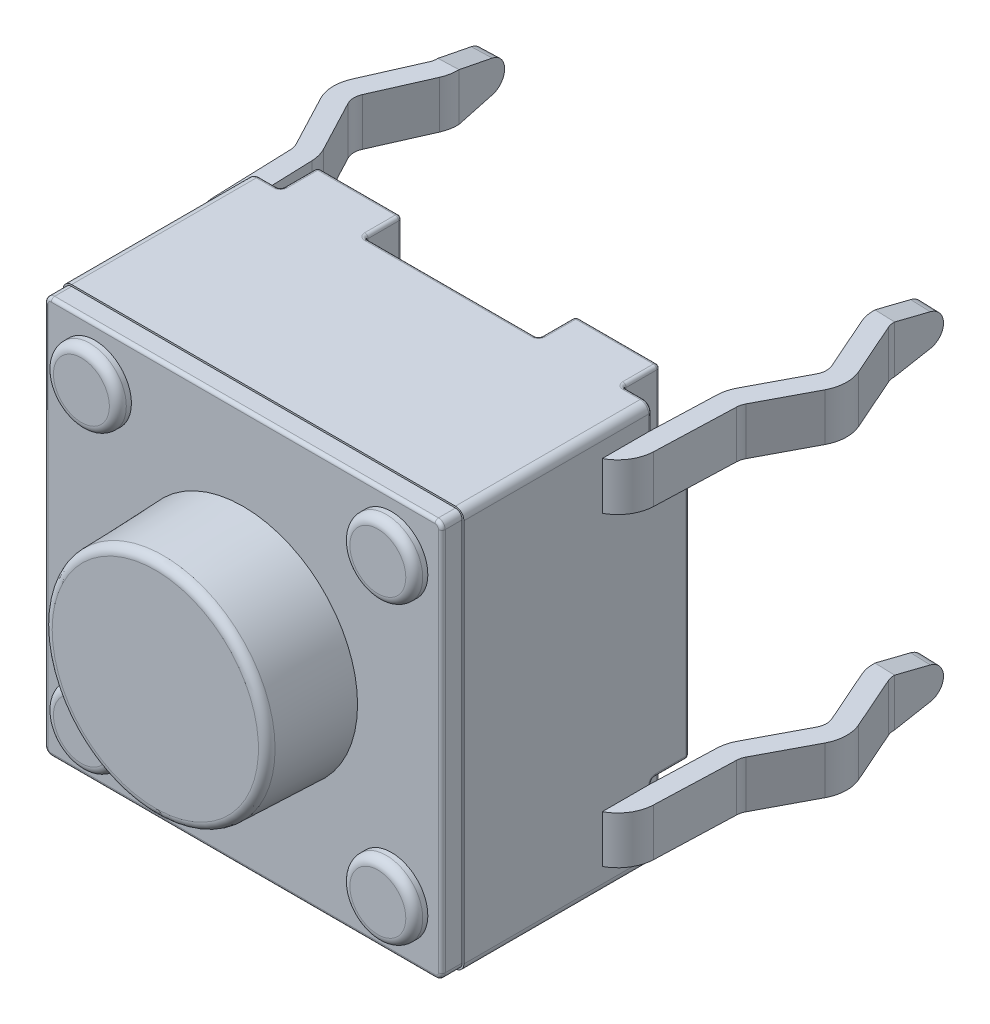
SolidWorks part; units mm, degrees
ref_plane "Front Plane" through (0, 0, 0) normal (0, 0, 1) x (1, 0, 0)
ref_plane "Top Plane" through (0, 0, 0) normal (0, 1, 0) x (1, 0, 0)
ref_plane "Right Plane" through (0, 0, 0) normal (1, 0, 0) x (0, 0, -1)
sketch "Sketch1" plane through (0, 0, 0) normal (0, 0, 1) x (1, 0, 0)
  line L1 (-3.0035, -3.0035) -> (3.0035, -3.0035)
  line L2 (-3.0035, -3.0035) -> (-3.0035, 3.0036)
  line L3 (-3.0035, 3.0036) -> (3.0035, 3.0036)
  line L4 (3.0035, -3.0035) -> (3.0035, 3.0036)
  line L5 (-3.0035, -3.0035) -> (3.0035, 3.0036) construction
  line L6 (-3.0035, 3.0036) -> (3.0035, -3.0035) construction
  point P0 (0, 0)
  dimension "D1" = 6.0071
  dimension "D2" = 6.0071
extrude "Boss-Extrude1" add sketch "Sketch1" along normal blind 2.8194 from offset 0.5588
fillet "Fillet1" radius 0.127 4 edges at (-3.0035, -3.0035, 1.9685) (-3.0035, 3.0036, 1.9685) (3.0035, 3.0036, 1.9685) (3.0035, -3.0035, 1.9685)
sketch "Sketch2" plane through (0, 0, 3.3782) normal (0, 0, -1) x (-1, 0, 0)
  line L8 (2.9781, -2.8765) -> (2.9781, 2.8765)
  line L9 (-2.8765, -2.9781) -> (2.8765, -2.9781)
  line L10 (-2.9781, 2.8765) -> (-2.9781, -2.8765)
  line L11 (2.8765, 2.9782) -> (-2.8765, 2.9782)
  line L12 (2.9781, -2.8765) -> (2.9781, 2.8765)
  line L13 (-2.8765, -2.9781) -> (2.8765, -2.9781)
  line L14 (-2.9781, 2.8765) -> (-2.9781, -2.8765)
  line L15 (2.8765, 2.9782) -> (-2.8765, 2.9782)
  arc A8 (2.8765, -2.9781) -> (2.9781, -2.8765) centre (2.8765, -2.8765) ccw
  arc A9 (-2.9781, -2.8765) -> (-2.8765, -2.9781) centre (-2.8765, -2.8765) ccw
  arc A10 (-2.8765, 2.9782) -> (-2.9781, 2.8765) centre (-2.8765, 2.8766) ccw
  arc A11 (2.9781, 2.8765) -> (2.8765, 2.9782) centre (2.8765, 2.8765) ccw
  arc A12 (2.8765, -2.9781) -> (2.9781, -2.8765) centre (2.8765, -2.8765) ccw
  arc A13 (-2.9781, -2.8765) -> (-2.8765, -2.9781) centre (-2.8765, -2.8765) ccw
  arc A14 (-2.8765, 2.9782) -> (-2.9781, 2.8765) centre (-2.8765, 2.8766) ccw
  arc A15 (2.9781, 2.8765) -> (2.8765, 2.9782) centre (2.8765, 2.8765) ccw
  dimension "D1" = 0.0254
extrude "Boss-Extrude2" add sketch "Sketch2" against normal blind 0.3048
sketch "Sketch3" plane through (0, 0, 0) normal (0, 0, 1) x (1, 0, 0)
  line L0 (-2.5662, -3.0035) -> (-2.5662, -1.8948)
  line L1 (-2.8765, -3.0035) -> (2.8765, -3.0035) construction
  line L2 (-2.5662, -1.8948) -> (-3.0035, -1.8948)
  line L3 (-3.0035, 2.8765) -> (-3.0035, -2.8765) construction
  line L4 (-2.4413, -0.5609) -> (-1.3018, -0.5609)
  line L5 (-1.3018, -0.5609) -> (-1.3017, -3.0035)
  line L6 (-2.4413, -0.5609) -> (-2.4413, 0.5609)
  line L7 (-2.5662, -3.0035) -> (-1.3017, -3.0035)
  line L8 (-3.0035, -1.8948) -> (-3.0035, 1.8948)
  line L9 (-2.4413, 0) -> (-3.0035, 0) construction
  line L10 (-2.5662, 3.0036) -> (-1.3017, 3.0035)
  line L11 (-1.3017, 0.5609) -> (-1.3017, 3.0035)
  line L12 (-2.4413, 0.5609) -> (-1.3017, 0.5609)
  line L13 (-2.5662, 1.8948) -> (-3.0035, 1.8948)
  line L14 (-2.5662, 3.0036) -> (-2.5662, 1.8948)
  line L15 (0, -3.0035) -> (0, 3.0036) construction
  line L16 (2.8765, 3.0036) -> (-2.8765, 3.0036) construction
  line L17 (2.4413, 0) -> (3.0035, 0) construction
  line L18 (2.5662, 3.0035) -> (2.5662, 1.8948)
  line L19 (2.5662, 1.8948) -> (3.0035, 1.8948)
  line L20 (2.4413, 0.5609) -> (1.3017, 0.5609)
  line L21 (1.3017, 0.5609) -> (1.3017, 3.0035)
  line L22 (2.5662, 3.0035) -> (1.3017, 3.0035)
  line L23 (3.0035, -1.8948) -> (3.0035, 1.8948)
  line L24 (2.5662, -3.0036) -> (1.3017, -3.0036)
  line L25 (2.4413, -0.5609) -> (2.4413, 0.5609)
  line L26 (1.3017, -0.5609) -> (1.3017, -3.0036)
  line L27 (2.4413, -0.5609) -> (1.3017, -0.5609)
  line L28 (2.5662, -1.8948) -> (3.0035, -1.8948)
  line L29 (2.5662, -3.0036) -> (2.5662, -1.8948)
  dimension "D1" = 1.7018
extrude "Boss-Extrude3" add sketch "Sketch3" along normal up to next
sketch "Sketch4" plane through (0, 0, 3.683) normal (0, 0, 1) x (1, 0, 0)
  line L1 (-2.2217, -2.2129) -> (2.2217, -2.2129) construction
  line L2 (-2.2217, -2.2129) -> (-2.2217, 2.2129) construction
  line L3 (-2.2217, 2.2129) -> (2.2217, 2.2129) construction
  line L4 (2.2217, -2.2129) -> (2.2217, 2.2129) construction
  line L5 (-2.2217, -2.2129) -> (2.2217, 2.2129) construction
  line L6 (-2.2217, 2.2129) -> (2.2217, -2.2129) construction
  circle A0 centre (2.2217, 2.2129) radius 0.5461
  circle A1 centre (-2.2217, 2.2129) radius 0.5461
  circle A2 centre (-2.2217, -2.2129) radius 0.5461
  circle A3 centre (2.2217, -2.2129) radius 0.5461
  point P0 (0, 0)
  dimension "D1" = 1.0922
extrude "Boss-Extrude4" add sketch "Sketch4" along normal blind 0.2032
sketch "Sketch5" plane through (0, 0, 3.683) normal (0, 0, 1) x (1, 0, 0)
  circle A0 centre (0, 0) radius 1.7145
  dimension "D1" = 3.429
extrude "Boss-Extrude5" add sketch "Sketch5" along normal offset from surface 5 draft 2
fillet "Fillet2" radius 0.127 5 edges at (-1.6756, 2.2129, 3.8862) (-1.6756, -2.2129, 3.8862) (2.7678, 2.2129, 3.8862) (2.7678, -2.2129, 3.8862) (-1.6685, 0, 5)
fillet "Fillet3" radius 0.0508 88 edges at (2.9664, -2.9664, 0.5588) (2.9664, 2.9664, 0.5588) (-2.9664, 2.9664, 0.5588) (-2.9664, -2.9664, 0.5588) (3.0035, -2.3857, 0.5588) (3.0035, 2.3857, 0.5588) (1.3017, -3.0036, 0.2794) (1.3017, 3.0035, 0.2794) (2.9484, 2.9484, 3.683) (0, 2.9782, 3.683) (-2.9484, 2.9484, 3.683) (-2.9781, 0, 3.683) (-2.9484, -2.9484, 3.683) (0, -2.9781, 3.683) (2.9484, -2.9484, 3.683) (2.4413, -0.5609, 0.2794) (1.3017, -0.5609, 0.2794) (1.3017, 0.5609, 0.2794) (2.4413, 0.5609, 0.2794) (-1.3018, -0.5609, 0.2794) (-2.4413, -0.5609, 0.2794) (-2.4413, 0.5609, 0.2794) (-1.3017, 0.5609, 0.2794) (2.7849, -1.8948, 0.5588) (3.0035, -1.8948, 0.2794) (2.5662, -3.0036, 0.2794) (2.5662, -2.4492, 0.5588) (2.5662, -1.8948, 0.2794) (3.0035, 1.8948, 0.2794) (2.7849, 1.8948, 0.5588) (2.5662, 1.8948, 0.2794) (2.5662, 2.4492, 0.5588) (2.5662, 3.0035, 0.2794) (-2.5662, 1.8948, 0.2794) (-2.5662, -1.8948, 0.2794) (-1.8715, 0.5609, 0.5588) (-2.4413, 0, 0.5588) (-1.8715, -0.5609, 0.5588) (1.3017, -1.7822, 0.5588) (1.8715, -0.5609, 0.5588) (2.4413, 0, 0.5588) (1.8715, 0.5609, 0.5588) (1.3017, 1.7822, 0.5588) (-1.3017, -1.7822, 0) (-1.8715, -0.5609, 0) (-2.4413, 0, 0) (-1.8715, 0.5609, 0) (-1.3017, 1.7822, 0) (-1.934, 3.0035, 0) (-2.5662, 2.4492, 0) (-2.7849, 1.8948, 0) (-3.0035, 0, 0) (-2.7849, -1.8948, 0) (-2.5662, -2.4492, 0) (-1.934, -3.0035, 0) (1.3017, 1.7822, 0) (1.8715, 0.5609, 0) (2.4413, 0, 0) (1.8715, -0.5609, 0) (1.3017, -1.7822, 0) (1.934, -3.0036, 0) (2.5662, -2.4492, 0) (2.7849, -1.8948, 0) (3.0035, 0, 0) (2.7849, 1.8948, 0) (2.5662, 2.4492, 0) (1.934, 3.0035, 0) (2.9781, 0, 3.683)
sketch "Sketch6" plane through (0, -3.0035, 0) normal (0, -1, 0) x (1, 0, 0)
  line L0 (-2.9873, 1.0641) -> (-3.0423, -0.5107)
  line L1 (-3.0423, -0.5107) -> (-3.5687, -1.5089)
  line L2 (-3.5687, -1.5089) -> (-3.1132, -2.5415)
  line L3 (-3.1132, -2.5415) -> (-3.1424, -3.3782)
  line L4 (-2.9873, 1.0641) -> (-2.5265, 1.0641)
  line L5 (-1.3525, 0) -> (-2.5154, 0) construction
  dimension "D1" = 4.445
  dimension "D2" = 3.3782
  dimension "D3" = 3.0226
  dimension "D4" = 3.5687
  dimension "D5" = 2.032
  dimension "D6" = 1.5748
  dimension "D7" = 92
extrude "Extrude-Thin1" add sketch "Sketch6" against normal blind 0.7112 from offset 0.3556 thin offset against normal yes
sketch "Sketch9" plane through (-3.3254, 0, 0.1161) normal (-0.9994, 0, 0.0349) x (0.0349, 0, 0.9994)
  line L0 (-2.7766, -2.6479) -> (-3.2944, -2.5316)
  line L1 (-3.2944, -2.0531) -> (-2.7766, -1.9367)
  line L3 (-2.7766, -2.6479) -> (-3.4858, -2.6479)
  line L4 (-3.4858, -2.6479) -> (-3.4858, -1.9367)
  line L5 (-3.4858, -1.9367) -> (-2.7766, -1.9367)
  arc A0 (-3.2944, -2.5316) -> (-3.2944, -2.0531) centre (-3.2406, -2.2923) cw
  point P2 (-3.4858, -1.9367)
  point P5 (-3.4858, -2.6479)
  point P7 (-2.7766, -1.9367)
  point P8 (-2.7766, -2.6479)
  line M1 (-3.4858, -2.6479) -> (-2.7766, -2.6479)
  line M3 (-2.7766, -1.9367) -> (-3.4858, -1.9367)
  line M4 (-3.4858, -1.9367) -> (-3.4858, -2.6479)
extrude "Cut-Extrude1" cut sketch "Sketch9" against normal blind 0.7112 contours L0 A0 L4 M1 | A0 L1 M4 M3
mirror "Mirror1" about plane through (0, 0, 0) normal (0, 1, 0) of "Extrude-Thin1", "Cut-Extrude1"
mirror "Mirror3" about plane through (0, 0, 0) normal (1, 0, 0) of "Mirror1", "Cut-Extrude1", "Extrude-Thin1"
